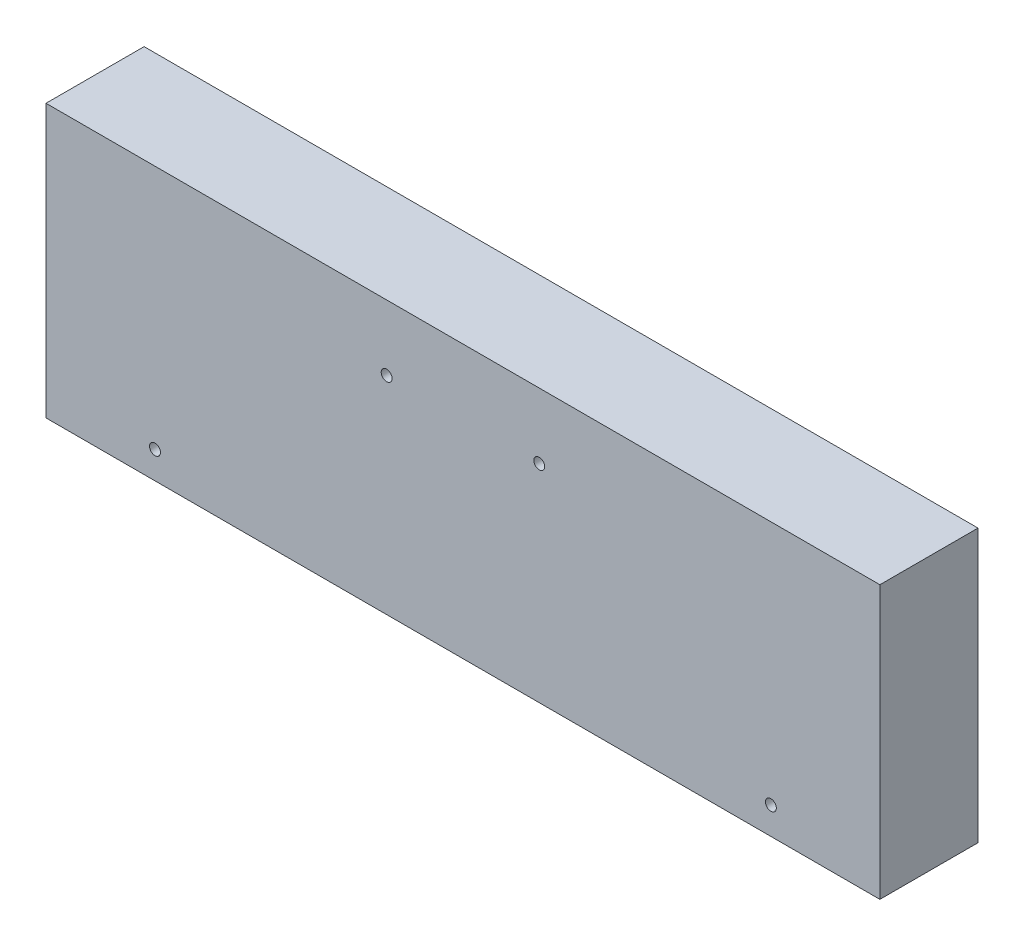
SolidWorks part; units mm, degrees
ref_plane "Front Plane" through (0, 0, 0) normal (0, 0, 1) x (1, 0, 0)
ref_plane "Top Plane" through (0, 0, 0) normal (0, 1, 0) x (1, 0, 0)
ref_plane "Right Plane" through (0, 0, 0) normal (1, 0, 0) x (0, 0, -1)
sketch "Sketch1" plane through (0, 0, 0) normal (0, 0, 1) x (1, 0, 0)
  line L0 (0, 45.315) -> (0, -47.1646) construction
  line L1 (-76.5, 25) -> (76.5, 25)
  line L2 (-76.5, 25) -> (-76.5, -25)
  line L3 (-76.5, -25) -> (76.5, -25)
  line L4 (76.5, 25) -> (76.5, -25)
  line L5 (-14, 41.0467) -> (-14, -27.3882) construction
  line L6 (14, 41.0467) -> (14, -27.3882) construction
  line L7 (-62.8862, 13) -> (40.242, 13) construction
  line L8 (-79.1057, 0) -> (82.6626, 0) construction
  line L9 (56.5, 35.2808) -> (56.5, -38.6838) construction
  line L10 (27.8412, -20) -> (79.4963, -20) construction
  line L11 (-56.5, 33.0185) -> (-56.5, -41.0794) construction
  line L12 (-100.2169, -20) -> (-49.5183, -20) construction
  circle A0 centre (-14, 13) radius 1
  circle A1 centre (14, 13) radius 1
  circle A2 centre (-56.5, -20) radius 1
  circle A3 centre (56.5, -20) radius 1
  dimension "D7" = 2
  dimension "D8" = 20
  dimension "D10" = 20
  dimension "D1" = 153
  dimension "D2" = 50
  dimension "D3" = 14
  dimension "D4" = 14
  dimension "D5" = 12
  dimension "D6" = 5
  dimension "D9" = 5
extrude "Boss-Extrude1" add sketch "Sketch1" along normal blind 18
